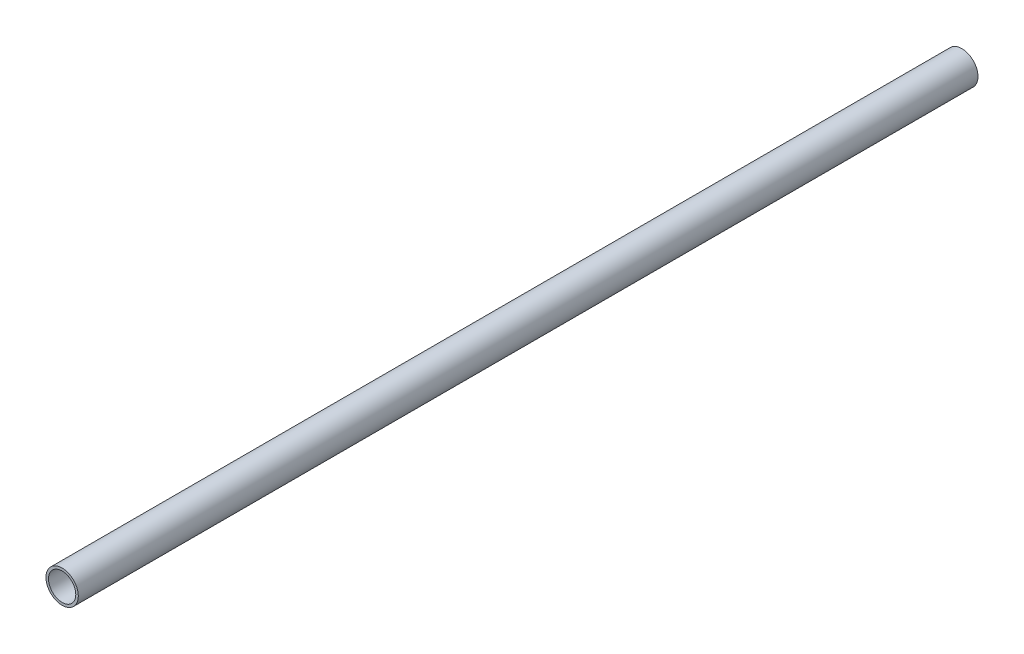
SolidWorks part; units mm, degrees
ref_plane "Front Plane" through (0, 0, 0) normal (0, 0, 1) x (1, 0, 0)
ref_plane "Top Plane" through (0, 0, 0) normal (0, 1, 0) x (1, 0, 0)
ref_plane "Right Plane" through (0, 0, 0) normal (1, 0, 0) x (0, 0, -1)
sketch "Sketch1" plane through (0, 0, 0) normal (0, 0, 1) x (1, 0, 0)
  line L0 (-7.9375, 0) -> (7.9375, 0) construction
  line L1 (0, -7.9375) -> (0, 7.9375) construction
  circle A0 centre (0, 0) radius 7.9375
  circle A1 centre (0, 0) radius 6.6929
  point P4 (0, 0)
  point P9 (0, 0)
  point P10 (6.6929, 0)
  dimension "ID" = 13.3858
  dimension "OD" = 15.875
  dimension "Wall Thickness" = 1.2446
sketch "Sketch2" plane through (0, 0, 0) normal (1, 0, 0) x (0, 0, -1)
  line L0 (220.8738, 7.9375) -> (-220.8738, 7.9375) construction
  line L1 (0, 7.9375) -> (0, -7.9375) construction
  point P3 (-202.6176, 7.9375)
  point P4 (0, 7.9375)
  point P5 (202.6176, 7.9375)
  dimension "Length" = 441.7476
  dimension "D1" = 18.2563
  dimension "D2" = 18.2562
sketch "Sketch3" plane through (0, 0, 0) normal (0, 0, 1) x (1, 0, 0)
  line L0 (0, -7.9375) -> (0, 7.9375) construction
  circle A0 centre (0, 0) radius 7.9375
  circle A1 centre (0, 0) radius 6.6929
  circle A2 centre (0, 0) radius 6.6929 construction
extrude "Boss-Extrude1" add sketch "Sketch3" along normal mid plane 441.7476
equation "\"D1@Boss-Extrude1\" = \"Length@Sketch2\""
equation "\"D1@Sketch2\"=\"OD@Sketch1\"*1.15"
equation "\"D2@Sketch2\"=\"D1@Sketch2\""
